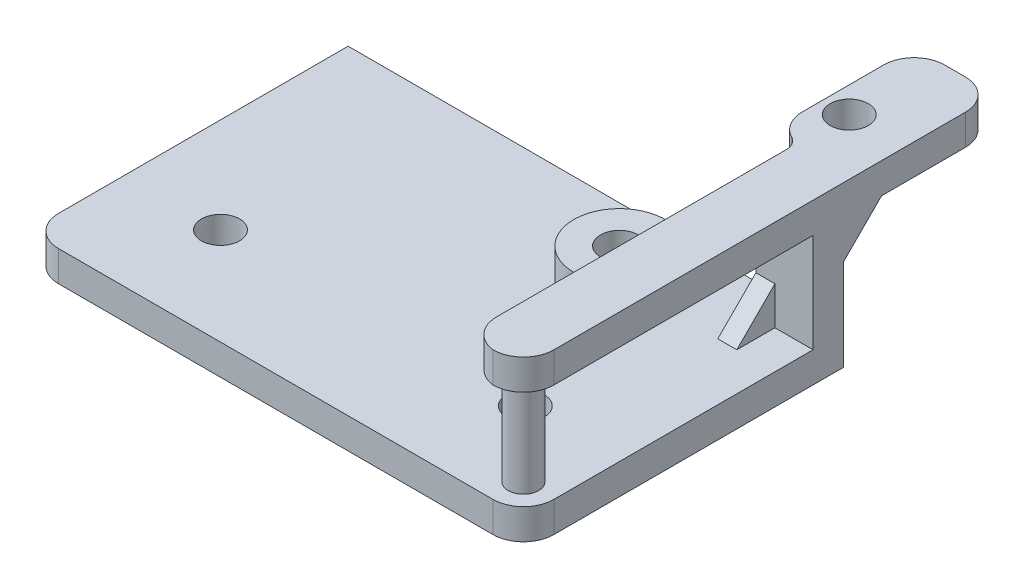
SolidWorks part; units mm, degrees
ref_plane "Front Plane" through (0, 0, 0) normal (0, 0, 1) x (1, 0, 0)
ref_plane "Top Plane" through (0, 0, 0) normal (0, 1, 0) x (1, 0, 0)
ref_plane "Right Plane" through (0, 0, 0) normal (1, 0, 0) x (0, 0, -1)
sketch "Sketch1" plane through (0, 0, 0) normal (0, 1, 0) x (1, 0, 0)
  line L1 (4, 0) -> (61, 0)
  line L2 (0, 4) -> (0, 42)
  line L3 (0, 42) -> (65, 42)
  line L4 (65, 4) -> (65, 42)
  arc A0 (65, 4) -> (61, 0) centre (61, 4) cw
  arc A1 (0, 4) -> (4, 0) centre (4, 4) ccw
  circle A2 centre (12.5, 12.75) radius 2.5
  circle A3 centre (52.5, 12.75) radius 2.5
  point P7 (65, 0)
  point P10 (0, 0)
  dimension "D3" = 4
  dimension "D8" = 5
  dimension "D9" = 5
  dimension "D1" = 42
  dimension "D2" = 65
  dimension "D4" = 12.75
  dimension "D5" = 40
  dimension "D6" = 12.75
  dimension "D7" = 12.5
extrude "Boss-Extrude1" add sketch "Sketch1" along normal blind 4
sketch "Sketch2" plane through (0, 4, 0) normal (0, 1, 0) x (1, 0, 0)
  line L0 (0, 42) -> (0, 4) construction
  line L1 (65, 42) -> (0, 42)
  line L2 (65, 42) -> (65, 38)
  line L3 (65, 38) -> (0, 38)
  line L4 (0, 42) -> (0, 38)
  circle A0 centre (61, 4) radius 2
  circle A1 centre (4, 4) radius 2
  dimension "D1" = 4
  dimension "D2" = 4
  dimension "D3" = 4
extrude "Boss-Extrude2" add sketch "Sketch2" along normal blind 13
sketch "Sketch3" plane through (0, 17, 0) normal (0, 1, 0) x (1, 0, 0)
  line L0 (4, 0) -> (61, 0) construction
  line L1 (0, 42) -> (65, 42)
  line L2 (0, 42) -> (0, 4)
  line L3 (4, 0) -> (61, 0)
  line L4 (65, 42) -> (65, 4)
  arc A0 (0, 4) -> (4, 0) centre (4, 4) ccw
  arc A1 (61, 0) -> (65, 4) centre (61, 4) ccw
  dimension "D1" = 4
  dimension "D2" = 0
  dimension "D3" = 65
extrude "Boss-Extrude3" add sketch "Sketch3" along normal blind 4
sketch "Sketch4" plane through (0, 0, -42) normal (0, 0, -1) x (-1, 0, 0)
  line L0 (-65, 21) -> (-65, 0) construction
  line L1 (-65, 17) -> (0, 17)
  line L2 (-65, 17) -> (-65, 21)
  line L3 (-65, 21) -> (0, 21)
  line L4 (0, 17) -> (0, 21)
  dimension "D1" = 4
extrude "Boss-Extrude4" add sketch "Sketch4" along normal blind 20
fillet "Fillet1" radius 4 2 edges at (65, 19, -62) (0, 19, -62)
sketch "Sketch6" plane through (0, 21, 0) normal (0, 1, 0) x (1, 0, 0)
  line L0 (65, 50.1043) -> (57.65, 50.1043)
  line L1 (4, 62) -> (61, 62) construction
  line L2 (57.65, 0) -> (57.65, 62)
  line L3 (65, 4) -> (65, 58) construction
  line L6 (45.5, 32.1043) -> (65, 32.1043)
  line L8 (45.5, 0) -> (45.5, 62)
  circle A0 centre (57.65, 50.1043) radius 2.5
  circle A1 centre (45.5, 32.1043) radius 2.5
  point P1 (0, 0)
  point P2 (0, 0)
  point P5 (0, 0)
  point P10 (0, 0)
  dimension "D2" = 5
  dimension "D3" = 0
  dimension "D4" = 5
  dimension "D1" = 62
  dimension "D5" = 62
  dimension "D6" = 29.8957
  dimension "D7" = 11.8957
  dimension "D8" = 0
  dimension "D9" = 0
  dimension "D10" = 7.35
  dimension "D11" = 12.15
  dimension "D12" = 7.35
  dimension "D13" = 11.8957
  dimension "D14" = 29.8957
extrude "Cut-Extrude1" cut sketch "Sketch6" against normal blind 20 contours L8 A1 | L8 A1 L6 | L6 A1 L8 | L2 A0 L0 | A0 region at (58.711, 21, -49.0433) region at (46.561, 21, -31.0433) region at (46.561, 21, -33.1654) region at (44.439, 21, -32.1043)
sketch "Sketch7" plane through (0, 0, 0) normal (0, 0, 1) x (1, 0, 0)
  line L0 (4, 21) -> (61, 21) construction
  line L1 (50, 21) -> (0, 21)
  line L2 (50, 21) -> (50, 0)
  line L3 (50, 0) -> (0, 0)
  line L4 (0, 21) -> (0, 0)
  line L5 (50, 4) -> (0, 4)
  line L6 (4, 4) -> (61, 4) construction
  line M5 (4, 17) -> (61, 17)
  line M7 (61, 21) -> (4, 21)
  line M8 (4, 21) -> (4, 17)
  dimension "D1" = 50
extrude "Cut-Extrude2" cut sketch "Sketch7" against normal blind 80 contours L5 L2 L1 L4 M5 M8 | L2 M7 M8 M5 region at (27, 19, 0) region at (24.4474, 10.7042, 0)
ref_plane "Plane1" through (57.5, 0, 0) normal (1, 0, 0) x (0, 0, -1)
sketch "Sketch10" plane through (57.5, 0, 0) normal (1, 0, 0) x (0, 0, -1)
  line L0 (33, 4) -> (38, 9)
  line L1 (4, 4) -> (38, 4) construction
  line L2 (38, 17) -> (38, 4) construction
  line L3 (38, 9) -> (38, 4)
  line L4 (38, 4) -> (33, 4)
  dimension "D1" = 5
  dimension "D2" = 5
extrude "Boss-Extrude6" add sketch "Sketch10" along normal blind 2.5 and the other way blind 2.5
sketch "Sketch11" plane through (0, 21, 0) normal (0, 1, 0) x (1, 0, 0)
  line L0 (57.5, 0) -> (57.5, 42)
  line L1 (50, 0) -> (61, 0) construction
  line L2 (57.5, -11.55) -> (57.5, 11.55) construction
  line L4 (50, 62) -> (50, 0) construction
  line L6 (50, 44) -> (50, 0)
  line L7 (50, 0) -> (57.5, 0)
  line L8 (55.5, 44) -> (50, 44)
  arc A2 (57.5, 42) -> (55.5, 44) centre (55.5, 42) ccw
  point P12 (57.5, 31)
  point P13 (57.5, 44)
  point P15 (50, 31)
  line M10 (50, 62) -> (50, 0)
  line M11 (50, 0) -> (61, 0)
  dimension "D1" = 44
  dimension "D3" = 2
  dimension "D2" = 7.5
extrude "Cut-Extrude3" cut sketch "Sketch11" against normal up to surface (17 mm away) contours L0 M10 M11 region at (53.7414, 21, -21.9438) up to face at (52.5, 4, -10.25)
fillet "Fillet2" radius 4 1 edges at (57.5, 19, 0)
sketch "Sketch8" plane through (0, 4, 0) normal (0, 1, 0) x (1, 0, 0)
  circle A0 centre (45.5, 32.1043) radius 6
  circle A1 centre (45.5, 32.1043) radius 2.5
  dimension "D1" = 5
  dimension "D2" = 12
extrude "Boss-Extrude5" add sketch "Sketch8" along normal blind 5
fillet "Fillet3" radius 4 1 edges at (50, 19, -62)
sketch "Sketch12" plane through (57.5, 0, 0) normal (1, 0, 0) x (0, 0, -1)
  line L0 (42, 12) -> (47, 17)
  line L1 (42, 17) -> (42, 0) construction
  line L2 (58, 17) -> (42, 17) construction
  line L3 (47, 17) -> (42, 17)
  line L4 (42, 17) -> (42, 12)
  dimension "D1" = 5
  dimension "D2" = 5
extrude "Boss-Extrude7" add sketch "Sketch12" along normal up to surface (7.5 mm away) from offset 4 up to face at (65, 11.8, -29.2)
sketch "Sketch13" plane through (0, 0, 0) normal (0, -1, 0) x (1, 0, 0)
  circle A0 centre (45.5, -32.1043) radius 4.5
  dimension "D1" = 9
extrude "Cut-Extrude4" cut sketch "Sketch13" against normal blind 6
sketch "Sketch14" plane through (0, 21, 0) normal (0, 1, 0) x (1, 0, 0)
  line L0 (54.2644, 44) -> (54.2644, 62)
  line L1 (55.5, 44) -> (50, 44) construction
  line L2 (54, 62) -> (61, 62) construction
  line L3 (54.2644, 62) -> (40.9821, 62)
  line L4 (40.9821, 62) -> (40.9821, 44)
  line L5 (40.9821, 44) -> (54.2644, 44)
  line L6 (50, 58) -> (50, 44) construction
  dimension "D1" = 13.2823
  dimension "D2" = 4.2644
extrude "Cut-Extrude5" cut sketch "Sketch14" against normal blind 6 contours L5 L0 L3 L4
fillet "Fillet5" radius 4 2 edges at (54.2644, 19, -62) (54.2644, 19, -44)
